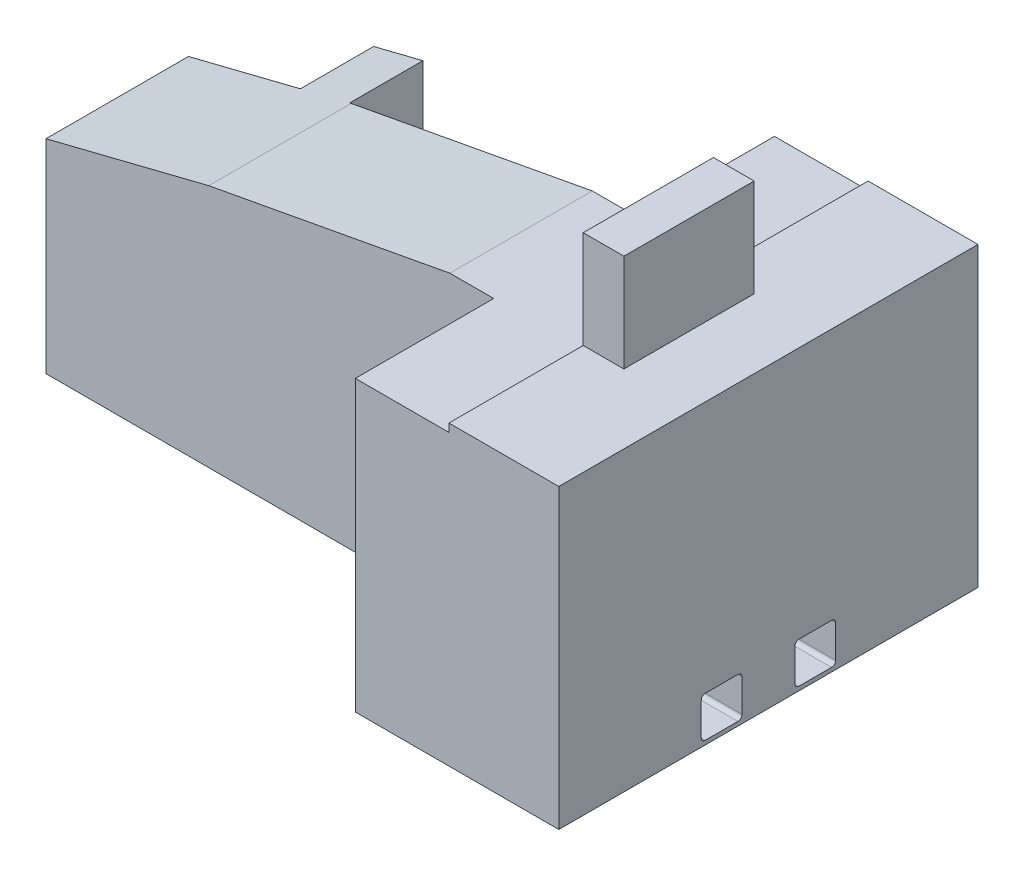
SolidWorks part; units mm, degrees
material "Custom Plastic"
ref_plane "Front Plane" through (0, 0, 0) normal (0, 0, 1) x (1, 0, 0)
ref_plane "Top Plane" through (0, 0, 0) normal (0, 1, 0) x (1, 0, 0)
ref_plane "Right Plane" through (0, 0, 0) normal (1, 0, 0) x (0, 0, -1)
sketch "Sketch1" plane through (0, 0, 0) normal (0, 0, 1) x (1, 0, 0)
  line L0 (-800, 0) -> (800, 0)
  line L1 (-800, 0) -> (-800, 500)
  line L2 (-400, 0) -> (-400, 600)
  line L3 (530, 0) -> (530, 970)
  line L4 (300, 0) -> (300, 730)
  line L5 (-800, 500) -> (-400, 600)
  line L6 (-400, 600) -> (300, 730)
  line L7 (300, 730) -> (530, 970)
  line L8 (800, 0) -> (530, 970)
  line L9 (-800, 500) -> (-800, 970)
  line L10 (-800, 970) -> (530, 970)
  dimension "D1" = 1600
  dimension "D2" = 500
  dimension "D3" = 400
  dimension "D4" = 800
  dimension "D5" = 600
  dimension "D6" = 270
  dimension "D7" = 500
  dimension "D8" = 970
  dimension "D9" = 730
sketch "Sketch2" plane through (0, 0, 0) normal (0, 1, 0) x (1, 0, 0)
  line L0 (800, -515) -> (800, 515)
  line L2 (800, -515) -> (300, -515)
  line L3 (300, -515) -> (300, -175)
  line L4 (300, -175) -> (-800, -175)
  line L5 (-800, -175) -> (-800, 175)
  line L6 (-800, 175) -> (-404, 175)
  line L7 (-404, 175) -> (-404, 355)
  line L8 (-404, 355) -> (-525, 355)
  line L9 (-525, 355) -> (-525, 175)
  line L10 (-525, 175) -> (300, 175)
  line L11 (300, 175) -> (300, 515)
  line L12 (300, 515) -> (800, 515)
  dimension "D1" = 800
  dimension "D2" = 500
  dimension "D3" = 175
  dimension "D4" = 175
  dimension "D5" = 530
  dimension "D6" = 121
  dimension "D7" = 500
  dimension "D8" = 350
  dimension "D9" = 1600
  dimension "D10" = 1030
  dimension "D11" = 515
  dimension "D12" = 275
extrude "Boss-Extrude1" add sketch "Sketch2" along normal blind 970 contours L12 L11 L10 L6 L5 L4 L3 L2 L0 | L8 L9 L6 L7 region at (207.7778, 0, 0) region at (-464.5, 0, -265)
extrude "Cut-Extrude1" cut sketch "Sketch1" against normal through all both and the other way through all contours L10 L9 L5 L6 L7 region at (-263.3113, 797.1661, 0)
sketch "Sketch3" plane through (-800, 0, 0) normal (-1, 0, 0) x (0, 0, 1)
  line L0 (-165, 0) -> (-65, 0)
  line L1 (175, 0) -> (-175, 0) construction
  line L2 (-55, 10) -> (-55, 120)
  line L3 (-55, 120) -> (-175, 120)
  line L4 (-175, 730) -> (-175, 0) construction
  line L5 (-175, 120) -> (-175, 10)
  line L11 (-165, 100) -> (-165, 20)
  line L12 (-155, 10) -> (-75, 10)
  line L13 (-65, 20) -> (-65, 100)
  line L14 (-75, 110) -> (-155, 110)
  line L19 (0, 137.8655) -> (0, -90.7951) construction
  line L20 (75, 110) -> (155, 110)
  line L21 (65, 20) -> (65, 100)
  line L22 (155, 10) -> (75, 10)
  line L23 (165, 100) -> (165, 20)
  line L24 (175, 120) -> (175, 10)
  line L25 (55, 120) -> (175, 120)
  line L26 (55, 10) -> (55, 120)
  line L27 (165, 0) -> (65, 0)
  arc A0 (175, 10) -> (165, 0) centre (165, 10) cw
  arc A1 (155, 10) -> (165, 20) centre (155, 20) ccw
  arc A2 (65, 20) -> (75, 10) centre (75, 20) ccw
  arc A3 (55, 10) -> (65, 0) centre (65, 10) ccw
  arc A4 (-65, 0) -> (-55, 10) centre (-65, 10) ccw
  arc A5 (-165, 0) -> (-175, 10) centre (-165, 10) cw
  arc A6 (-165, 20) -> (-155, 10) centre (-155, 20) ccw
  arc A7 (-75, 10) -> (-65, 20) centre (-75, 20) ccw
  arc A8 (-65, 100) -> (-75, 110) centre (-75, 100) ccw
  arc A9 (-165, 100) -> (-155, 110) centre (-155, 100) cw
  arc A10 (155, 110) -> (165, 100) centre (155, 100) cw
  arc A11 (75, 110) -> (65, 100) centre (75, 100) ccw
  point P27 (175, 0)
  point P30 (165, 10)
  point P33 (65, 10)
  point P36 (55, 0)
  point P39 (-55, 0)
  point P42 (-175, 0)
  point P45 (-165, 10)
  point P48 (-65, 10)
  point P51 (-65, 110)
  point P54 (-165, 110)
  point P57 (165, 110)
  point P60 (65, 110)
  dimension "D3" = 10
  dimension "D4" = 10
  dimension "D1" = 120
  dimension "D2" = 120
  dimension "D5" = 100
  dimension "D6" = 100
  dimension "D8" = 10
  dimension "D9" = 10
extrude "Cut-Extrude5" cut sketch "Sketch3" against normal blind 1625 contours A9 L11 A6 L12 A7 L13 A8 L14 | L21 A2 L22 A1 L23 L20 region at (-800, 60, -115) region at (-800, 60, 115)
sketch "Sketch4" plane through (0, 0, 0) normal (0, -1, 0) x (1, 0, 0)
  line L0 (-1069.2255, 0) -> (880.5229, 0) construction
  line L1 (0, 391.8823) -> (0, -321.383) construction
  line L2 (300, 175) -> (-800, 175) construction
  line L3 (-800, -175) -> (-525, -175) construction
  circle A0 centre (-498.5, 115) radius 8.5
  circle A1 centre (-501, -115) radius 8.5
  circle A2 centre (501, -115) radius 8.5
  circle A3 centre (498.5, 115) radius 8.5
  dimension "D1" = 17
  dimension "D4" = 17
  dimension "D2" = 498.5
  dimension "D3" = 60
  dimension "D5" = 501
  dimension "D6" = 60
extrude "Cut-Extrude6" cut sketch "Sketch4" against normal blind 78
sketch "Sketch5" plane through (0, 0, 515) normal (0, 0, 1) x (1, 0, 0)
  line L1 (800, 970) -> (800, 0) construction
  line L3 (800, 970) -> (530, 970) construction
  line L4 (630, 970) -> (530, 970)
  line L5 (530, 970) -> (530, 710)
  line L6 (530, 710) -> (155, 710)
  line L7 (800, 0) -> (300, 0) construction
  line L9 (155, 650) -> (155, 710)
  line L10 (800, 730) -> (630, 730)
  line L11 (800, 730) -> (800, 650)
  line L12 (630, 970) -> (630, 730)
  line L13 (155, 650) -> (800, 650)
  line L14 (155, 710) -> (155, 970)
  line L15 (155, 970) -> (800, 970)
  line L16 (800, 970) -> (800, 730)
  line M1 (530, 970) -> (300, 730)
  line M2 (300, 730) -> (300, 0)
  line M4 (800, 0) -> (800, 970)
  line M5 (800, 970) -> (530, 970)
  dimension "D1" = 170
  dimension "D2" = 100
  dimension "D3" = 375
  dimension "D4" = 710
  dimension "D5" = 650
  dimension "D6" = 730
extrude "Cut-Extrude8" cut sketch "Sketch5" against normal blind 1478 contours L15 L14 L6 M2 M1 | L6 L5 M1 M2 | L12 L10 M5 M4 region at (715, 850, 515) region at (290.5475, 861.1332, 515) region at (447.8571, 797.1429, 515)
sketch "Sketch6" plane through (0, 970, 0) normal (0, 1, 0) x (1, 0, 0)
  line L0 (530, 135) -> (530, -185)
  line L1 (530, 515) -> (530, -515) construction
  line L2 (530, 515) -> (530, -515) construction
  line L3 (530, -185) -> (630, -185)
  line L4 (630, 515) -> (630, -515) construction
  line L5 (630, -185) -> (630, 135)
  line L6 (630, 515) -> (630, -515) construction
  line L7 (630, 135) -> (530, 135)
  line L8 (530, 515) -> (630, 515) construction
  dimension "D1" = 380
  dimension "D2" = 700
extrude "Cut-Extrude9" cut sketch "Sketch6" against normal blind 240 flip side to cut
